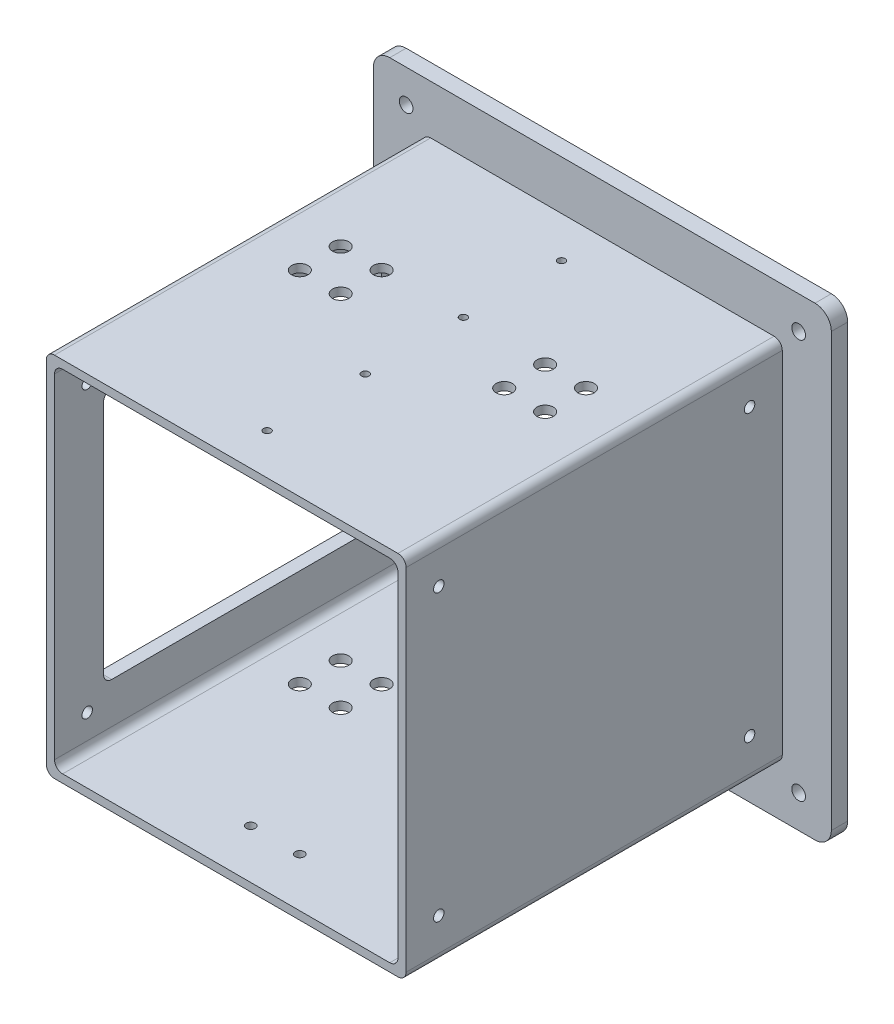
SolidWorks part; units mm, degrees
ref_plane "前视基准面" through (0, 0, 0) normal (0, 0, 1) x (1, 0, 0)
ref_plane "上视基准面" through (0, 0, 0) normal (0, 1, 0) x (1, 0, 0)
ref_plane "右视基准面" through (0, 0, 0) normal (1, 0, 0) x (0, 0, -1)
sketch "草图1" plane through (0, 0, 0) normal (0, 0, 1) x (1, 0, 0)
  line L1 (-105, -107.125) -> (105, -107.125)
  line L2 (-105, -107.125) -> (-105, 107.125)
  line L3 (-105, 107.125) -> (105, 107.125)
  line L4 (105, -107.125) -> (105, 107.125)
  line L5 (-105, -107.125) -> (105, 107.125) construction
  line L6 (-105, 107.125) -> (105, -107.125) construction
  line L7 (-110, -112.125) -> (110, -112.125)
  line L8 (-110, -112.125) -> (-110, 112.125)
  line L9 (-110, 112.125) -> (110, 112.125)
  line L10 (110, -112.125) -> (110, 112.125)
  line L11 (-110, -112.125) -> (110, 112.125) construction
  line L12 (-110, 112.125) -> (110, -112.125) construction
  point P0 (0, 0)
  point P6 (0, 0)
  dimension "D1" = 210
  dimension "D2" = 214.25
  dimension "D3" = 5
  dimension "D4" = 5
extrude "凸台-拉伸1" add sketch "草图1" along normal blind 230
sketch "草图2" plane through (0, 0, 0) normal (0, 0, -1) x (-1, 0, 0)
  line L0 (-110, 112.125) -> (110, 112.125) construction
  line L1 (-140, -142.125) -> (140, -142.125)
  line L2 (-140, -142.125) -> (-140, 142.125)
  line L3 (-140, 142.125) -> (140, 142.125)
  line L4 (140, -142.125) -> (140, 142.125)
  line L5 (-140, -142.125) -> (140, 142.125) construction
  line L6 (-140, 142.125) -> (140, -142.125) construction
  line L7 (-110, -112.125) -> (-110, 112.125) construction
  line L8 (105, 107.125) -> (105, -107.125) construction
  line L9 (105, -107.125) -> (-105, -107.125) construction
  line L10 (-105, -107.125) -> (-105, 107.125) construction
  line L11 (-105, 107.125) -> (105, 107.125) construction
  line L12 (105, 107.125) -> (105, -107.125)
  line L13 (105, -107.125) -> (-105, -107.125)
  line L14 (-105, -107.125) -> (-105, 107.125)
  line L15 (-105, 107.125) -> (105, 107.125)
  point P0 (0, 0)
  dimension "D1" = 30
  dimension "D2" = 30
extrude "凸台-拉伸2" add sketch "草图2" along normal blind 10
fillet "圆角1" radius 5 4 edges at (110, 112.125, 115) (110, -112.125, 115) (-110, -112.125, 115) (-110, 112.125, 115)
fillet "圆角2" radius 5 4 edges at (105, 107.125, 110) (-105, 107.125, 110) (105, -107.125, 110) (-105, -107.125, 110)
fillet "圆角3" radius 10 4 edges at (-140, 142.125, -5) (140, 142.125, -5) (140, -142.125, -5) (-140, -142.125, -5)
hole_wizard "Ø8.4 (8.4) 直径孔1" positions "草图3" profile "草图4" hole size "Ø8.4" standard "GB" end condition through all
sketch "草图3" plane through (0, 0, 0) normal (0, 0, 1) x (1, 0, 0)
  line L0 (130, -142.125) -> (-130, -142.125) construction
  line L1 (140, 132.125) -> (140, -132.125) construction
  line L2 (-140, -132.125) -> (-140, 132.125) construction
  line L3 (-130, 142.125) -> (130, 142.125) construction
  point P0 (120, 122.125)
  point P3 (120, -122.125)
  point P6 (-120, -122.125)
  point P10 (-120, 122.125)
  dimension "D1" = 20
  dimension "D2" = 20
  dimension "D3" = 20
  dimension "D4" = 20
  dimension "D5" = 20
  dimension "D6" = 20
  dimension "D7" = 20
  dimension "D8" = 20
sketch "草图4" plane through (120, 122.125, 0) normal (1, 0, 0) x (0, -1, 0)
  line L0 (0, 0) -> (0, 10)
  line L1 (0, 10) -> (4.2, 10)
  line L2 (4.2, 10) -> (4.2, 0)
  line L5 (4.2, 0) -> (0, 0)
  line L11 (0, -6.35) -> (0, 107.95) construction
  dimension "通孔孔直径" = 8.4
  dimension "通孔孔深度" = 10
sketch "草图18" plane through (0, 112.125, 0) normal (0, 1, 0) x (1, 0, 0)
  line L0 (105, -230) -> (-105, -230) construction
  line L1 (-105, 0) -> (-105, -230) construction
  line L2 (105, -230) -> (105, 0) construction
  point P0 (-75, -85)
  point P1 (-75, -110)
  point P2 (-50, -110)
  point P3 (-50, -85)
  point P5 (50, -110)
  point P6 (75, -110)
  point P8 (75, -85)
  point P16 (50, -85)
  dimension "D1" = 25
  dimension "D2" = 25
  dimension "D3" = 35.3553
  dimension "D4" = 25
  dimension "D5" = 35.3553
  dimension "D6" = 25
  dimension "D7" = 30
  dimension "D8" = 30
  dimension "D9" = 25
  dimension "D10" = 25
  dimension "D11" = 25
  dimension "D12" = 25
  dimension "D13" = 120
  dimension "D14" = 120
  dimension "D15" = 35.3553
  dimension "D16" = 55
hole_wizard "大小mm 暗销孔11" positions "草图33" profile "草图34" hole size "Ø10.0" standard "GB" end condition through all
sketch "草图33" plane through (0, 112.125, 0) normal (0, 1, 0) x (1, 0, 0)
  point P0 (-75, -85)
  point P3 (-50, -85)
  point P6 (-50, -110)
  point P9 (-75, -110)
  point P12 (50, -110)
  point P15 (50, -85)
  point P18 (75, -85)
  point P21 (75, -110)
sketch "草图34" plane through (-75, 112.125, 85) normal (1, 0, 0) x (0, 0, 1)
  line L0 (0, 0) -> (0, 254.25)
  line L1 (0, 254.25) -> (5, 254.25)
  line L2 (5, 254.25) -> (5, 0)
  line L5 (5, 0) -> (0, 0)
  line L11 (0, -6.35) -> (0, 107.95) construction
  dimension "通孔孔直径" = 10
  dimension "通孔孔深度" = 254.25
sketch "草图35" plane through (0, -112.125, 0) normal (0, -1, 0) x (1, 0, 0)
  line L0 (130, 0) -> (-130, 0) construction
  line L2 (-105, 0) -> (105, 0) construction
  line L3 (105, 0) -> (105, 230) construction
  line L4 (-105, 230) -> (-105, 0) construction
  point P0 (15, 200)
  point P1 (19, 25.5)
  point P2 (-19, 25.5)
  point P4 (-15, 200)
  dimension "D1" = 90
  dimension "D2" = 38
  dimension "D4" = 19
  dimension "D5" = 200
  dimension "D6" = 200
  dimension "D7" = 25.5
  dimension "D8" = 25.5
  dimension "D9" = 90
sketch "草图38" plane through (0, 112.125, 0) normal (0, 1, 0) x (1, 0, 0)
  line L0 (-105, 0) -> (-105, -230) construction
  line L2 (105, 0) -> (-105, 0) construction
  point P0 (0, -25)
  point P1 (0, -85)
  point P2 (0, -205)
  point P3 (0, -145)
  dimension "D1" = 105
  dimension "D2" = 60
  dimension "D3" = 60
  dimension "D4" = 60
  dimension "D5" = 25
  dimension "D6" = 105
  dimension "D7" = 105
  dimension "D8" = 105
hole_wizard "Ø4.5 (4.5) 直径孔1" positions "草图39" profile "草图40" hole size "Ø4.5" standard "GB" end condition up to next
sketch "草图39" plane through (0, 112.125, 0) normal (0, 1, 0) x (1, 0, 0)
  point P0 (0, -25)
  point P3 (0, -85)
  point P6 (0, -145)
  point P9 (0, -205)
sketch "草图40" plane through (0, 112.125, 25) normal (1, 0, 0) x (0, 0, 1)
  line L0 (0, 0) -> (0, 5)
  line L1 (0, 5) -> (2.25, 5)
  line L2 (2.25, 5) -> (2.25, 0)
  line L5 (2.25, 0) -> (0, 0)
  line L11 (0, -6.35) -> (0, 107.95) construction
  dimension "通孔孔直径" = 4.5
  dimension "通孔孔深度" = 5
hole_wizard "Ø6.6 (6.6) 直径孔1" positions "草图41" profile "草图42" hole size "Ø6.6" standard "GB" end condition up to next
sketch "草图41" plane through (0, -112.125, 0) normal (0, -1, 0) x (-1, 0, 0)
  point P0 (19, -25.5)
  point P3 (-19, -25.5)
sketch "草图42" plane through (-19, -112.125, 25.5) normal (1, 0, 0) x (0, 0, -1)
  line L0 (0, 0) -> (0, 5)
  line L1 (0, 5) -> (3.3, 5)
  line L2 (3.3, 5) -> (3.3, 0)
  line L5 (3.3, 0) -> (0, 0)
  line L11 (0, -6.35) -> (0, 107.95) construction
  dimension "通孔孔直径" = 6.6
  dimension "通孔孔深度" = 5
hole_wizard "Ø5.5 (5.5) 直径孔1" positions "草图43" profile "草图44" hole size "Ø5.5" standard "GB" end condition up to next
sketch "草图43" plane through (0, -112.125, 0) normal (0, -1, 0) x (-1, 0, 0)
  point P0 (15, -200)
  point P3 (-15, -200)
sketch "草图44" plane through (-15, -112.125, 200) normal (1, 0, 0) x (0, 0, -1)
  line L0 (0, 0) -> (0, 5)
  line L1 (0, 5) -> (2.75, 5)
  line L2 (2.75, 5) -> (2.75, 0)
  line L5 (2.75, 0) -> (0, 0)
  line L11 (0, -6.35) -> (0, 107.95) construction
  dimension "通孔孔直径" = 5.5
  dimension "通孔孔深度" = 5
sketch "草图45" plane through (-110, 0, 0) normal (-1, 0, 0) x (0, 0, 1)
  line L0 (230, 107.125) -> (0, 107.125) construction
  line L1 (200, -77.125) -> (30, -77.125)
  line L2 (200, -77.125) -> (200, 77.125)
  line L3 (200, 77.125) -> (30, 77.125)
  line L4 (30, -77.125) -> (30, 77.125)
  line L5 (200, -77.125) -> (30, 77.125) construction
  line L6 (200, 77.125) -> (30, -77.125) construction
  line L7 (0, -107.125) -> (230, -107.125) construction
  line L8 (0, -132.125) -> (0, 132.125) construction
  line L9 (230, 107.125) -> (230, -107.125) construction
  point P0 (115, 0)
  dimension "D1" = 30
  dimension "D2" = 30
  dimension "D3" = 30
  dimension "D4" = 30
extrude "切除-拉伸1" cut sketch "草图45" against normal up to next
fillet "圆角4" radius 5 4 edges at (-107.5, -77.125, 30) (-107.5, -77.125, 200) (-107.5, 77.125, 200) (-107.5, 77.125, 30)
sketch "草图46" plane through (110, 0, 0) normal (1, 0, 0) x (0, 0, -1)
  line L0 (-195, 77.125) -> (-35, 77.125) construction
  line L1 (-200, -72.125) -> (-200, 72.125) construction
  line L2 (-30, 72.125) -> (-30, -72.125) construction
  line L3 (-35, -77.125) -> (-195, -77.125) construction
  point P0 (-210, 87.125)
  point P1 (-210, -87.125)
  point P2 (-20, -87.125)
  point P3 (-20, 87.125)
  dimension "D1" = 10
  dimension "D2" = 10
  dimension "D3" = 10
  dimension "D4" = 10
  dimension "D5" = 10
  dimension "D6" = 10
  dimension "D7" = 10
  dimension "D8" = 10
hole_wizard "Ø6.4 (6.4) 直径孔1" positions "草图47" profile "草图48" hole size "Ø6.4" standard "GB" end condition through all
sketch "草图47" plane through (110, 0, 0) normal (1, 0, 0) x (0, 0, -1)
  point P0 (-210, 87.125)
  point P3 (-20, 87.125)
  point P6 (-20, -87.125)
  point P9 (-210, -87.125)
sketch "草图48" plane through (110, 87.125, 210) normal (0, 1, 0) x (0, 0, -1)
  line L0 (0, 0) -> (0, 250)
  line L1 (0, 250) -> (3.2, 250)
  line L2 (3.2, 250) -> (3.2, 0)
  line L5 (3.2, 0) -> (0, 0)
  line L11 (0, -6.35) -> (0, 107.95) construction
  dimension "通孔孔直径" = 6.4
  dimension "通孔孔深度" = 250
sketch "草图49" plane through (-110, 0, 0) normal (-1, 0, 0) x (0, 0, 1)
  line L0 (195, 77.125) -> (35, 77.125) construction
  line L1 (27, 80.125) -> (203, 80.125)
  line L2 (27, 80.125) -> (27, -80.125)
  line L3 (27, -80.125) -> (203, -80.125)
  line L4 (203, 80.125) -> (203, -80.125)
  line L5 (35, -77.125) -> (195, -77.125) construction
  line L6 (30, 72.125) -> (30, -72.125) construction
  line L7 (200, -72.125) -> (200, 72.125) construction
  line L8 (200, -72.125) -> (200, 72.125)
  line L9 (35, -77.125) -> (195, -77.125)
  line L10 (30, 72.125) -> (30, -72.125)
  line L11 (195, 77.125) -> (35, 77.125)
  arc A0 (200, 72.125) -> (195, 77.125) centre (195, 72.125) ccw construction
  arc A1 (195, -77.125) -> (200, -72.125) centre (195, -72.125) ccw construction
  arc A2 (30, -72.125) -> (35, -77.125) centre (35, -72.125) ccw construction
  arc A3 (35, 77.125) -> (30, 72.125) centre (35, 72.125) ccw construction
  arc A4 (200, 72.125) -> (195, 77.125) centre (195, 72.125) ccw
  arc A5 (195, -77.125) -> (200, -72.125) centre (195, -72.125) ccw
  arc A6 (30, -72.125) -> (35, -77.125) centre (35, -72.125) ccw
  arc A7 (35, 77.125) -> (30, 72.125) centre (35, 72.125) ccw
  dimension "D1" = 3
  dimension "D2" = 3
  dimension "D3" = 3
  dimension "D4" = 3
extrude "凸台-拉伸3" add sketch "草图49" along normal blind 3
fillet "圆角5" radius 5 4 edges at (-111.5, 80.125, 27) (-111.5, -80.125, 27) (-111.5, -80.125, 203) (-111.5, 80.125, 203)
sketch "草图50" plane through (0, 0, -10) normal (0, 0, -1) x (-1, 0, 0)
  line L0 (100, 107.125) -> (-100, 107.125) construction
  line L1 (108, -110.125) -> (-108, -110.125)
  line L2 (108, -110.125) -> (108, 110.125)
  line L3 (108, 110.125) -> (-108, 110.125)
  line L4 (-108, -110.125) -> (-108, 110.125)
  line L5 (108, -110.125) -> (-108, 110.125) construction
  line L6 (108, 110.125) -> (-108, -110.125) construction
  line L7 (-105, 102.125) -> (-105, -102.125) construction
  line L8 (-100, -107.125) -> (100, -107.125) construction
  line L9 (105, -102.125) -> (105, 102.125) construction
  line L10 (-100, -107.125) -> (100, -107.125)
  line L11 (105, -102.125) -> (105, 102.125)
  line L12 (100, 107.125) -> (-100, 107.125)
  line L13 (-105, 102.125) -> (-105, -102.125)
  arc A0 (-105, -102.125) -> (-100, -107.125) centre (-100, -102.125) ccw construction
  arc A1 (100, -107.125) -> (105, -102.125) centre (100, -102.125) ccw construction
  arc A2 (105, 102.125) -> (100, 107.125) centre (100, 102.125) ccw construction
  arc A3 (-100, 107.125) -> (-105, 102.125) centre (-100, 102.125) ccw construction
  arc A4 (-105, -102.125) -> (-100, -107.125) centre (-100, -102.125) ccw
  arc A5 (100, -107.125) -> (105, -102.125) centre (100, -102.125) ccw
  arc A6 (105, 102.125) -> (100, 107.125) centre (100, 102.125) ccw
  arc A7 (-100, 107.125) -> (-105, 102.125) centre (-100, 102.125) ccw
  point P0 (0, 0)
  dimension "D1" = 3
  dimension "D2" = 3
extrude "凸台-拉伸4" add sketch "草图50" along normal blind 3
fillet "圆角6" radius 5 4 edges at (-108, 110.125, -11.5) (-108, -110.125, -11.5) (108, -110.125, -11.5) (108, 110.125, -11.5)
